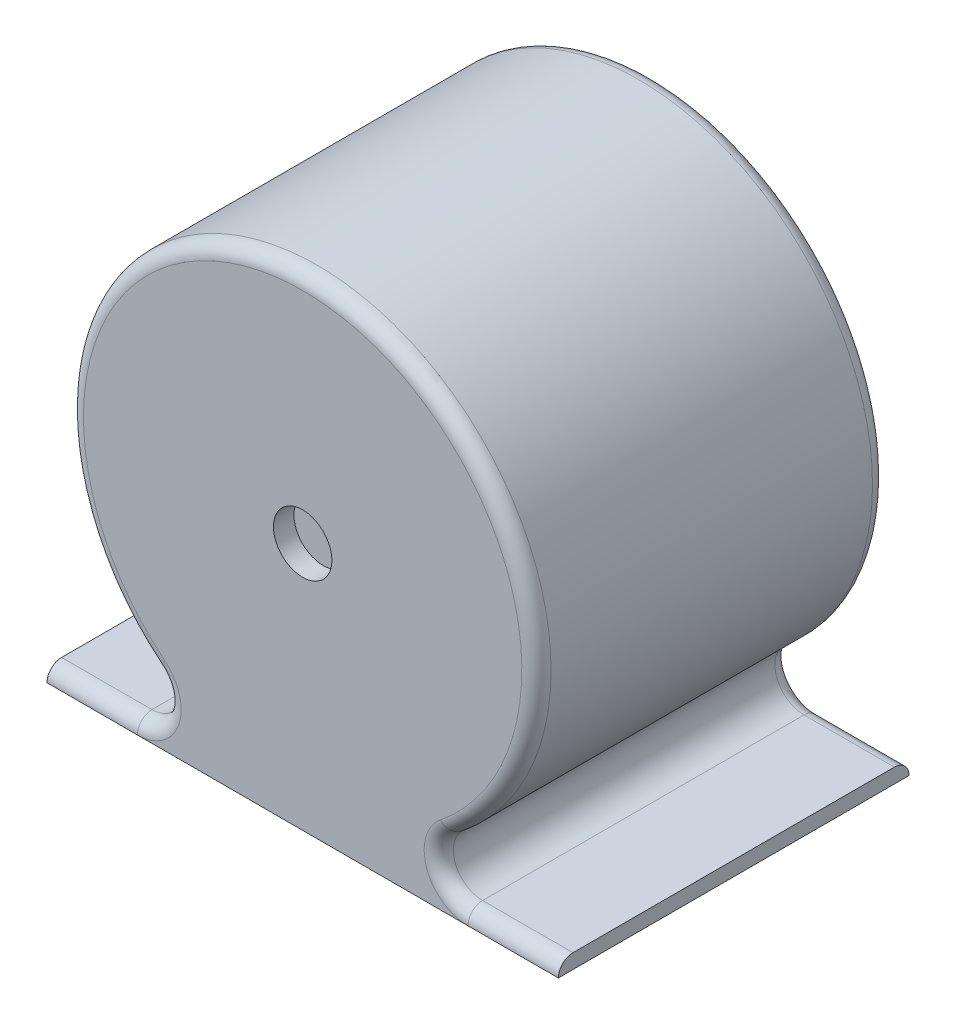
SolidWorks part; units mm, degrees
ref_plane "Front Plane" through (0, 0, 0) normal (0, 0, 1) x (1, 0, 0)
ref_plane "Top Plane" through (0, 0, 0) normal (0, 1, 0) x (1, 0, 0)
ref_plane "Right Plane" through (0, 0, 0) normal (1, 0, 0) x (0, 0, -1)
sketch "Sketch1" plane through (0, 0, 0) normal (0, 0, 1) x (1, 0, 0)
  line L0 (-55.5625, -53.975) -> (55.5625, -53.975)
  line L1 (-55.5625, -53.975) -> (-55.5625, -50.8)
  line L2 (-55.5625, -50.8) -> (55.5625, -50.8)
  line L3 (55.5625, -50.8) -> (55.5625, -53.975)
  circle A0 centre (0, 0) radius 50.8
  arc A1 (-35.921, -50.8) -> (-31.9298, -39.5111) centre (-35.921, -44.45) ccw
  arc A2 (35.921, -50.8) -> (31.9298, -39.5111) centre (35.921, -44.45) cw
  point P6 (0, -53.975)
  dimension "D1" = 101.6
  dimension "D4" = 6.35
  dimension "D2" = 104.775
  dimension "D3" = 111.125
extrude "Boss-Extrude1" add sketch "Sketch1" along normal mid plane 76.2 contours A0 | A1 L2 A0 | L2 A2 A0 | L3 L2 L1 L0 region at (0, -52.3875, 0) region at (-23.1819, -48.035, 0) region at (23.1819, -48.035, 0) region at (0, 0, 0)
sketch "Sketch2" plane through (0, 0, 38.1) normal (0, 0, 1) x (1, 0, 0)
  circle A0 centre (0, 0) radius 6.35
  dimension "D1" = 12.7
extrude "Cut-Extrude1" cut sketch "Sketch2" against normal blind 4.445
fillet "Fillet1" radius 3.175 10 edges at (45.7418, -50.8, 38.1) (29.9342, -46.5667, 38.1) (-45.7418, -50.8, 38.1) (-29.9342, -46.5667, 38.1) (45.7418, -50.8, -38.1) (29.9342, -46.5667, -38.1) (-45.7418, -50.8, -38.1) (-29.9342, -46.5667, -38.1) (0, 50.8, 38.1) (0, 50.8, -38.1)
